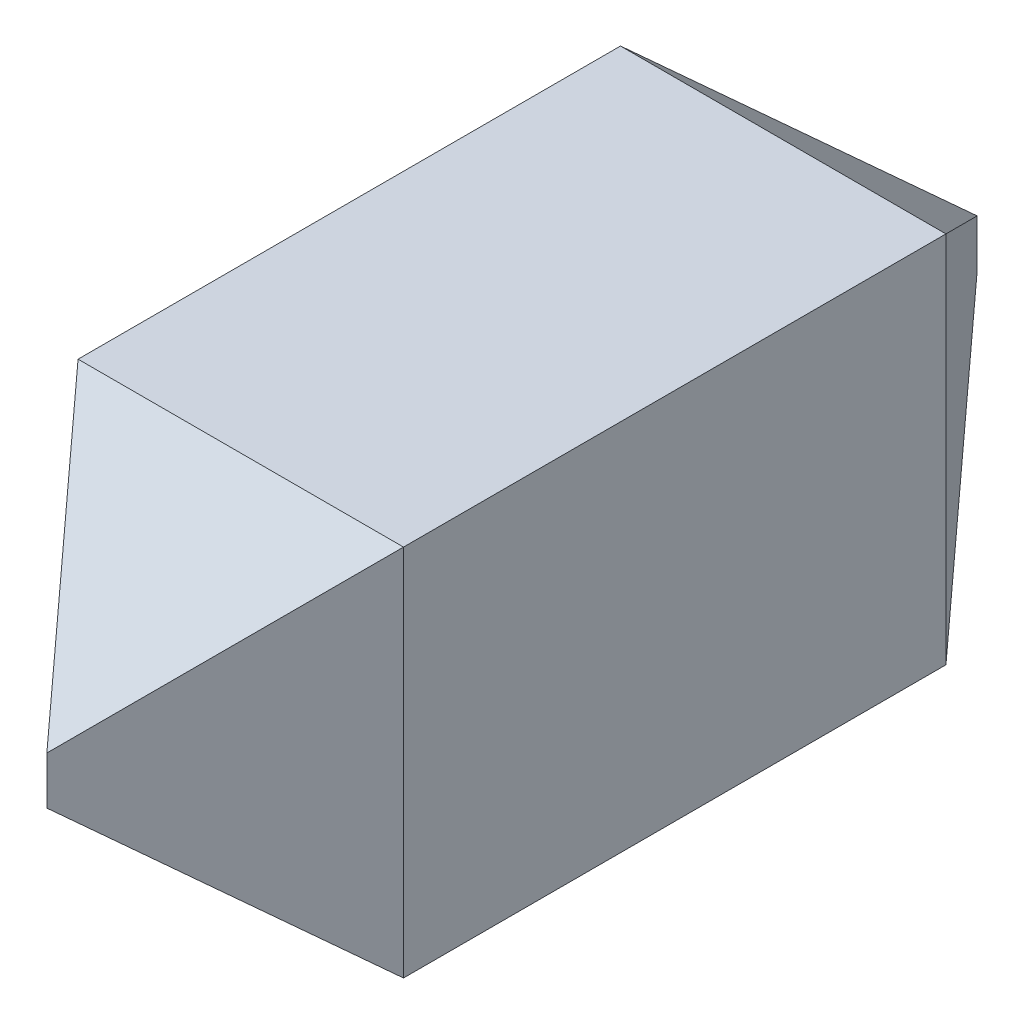
SolidWorks part; units mm, degrees
ref_plane "Front Plane" through (0, 0, 0) normal (0, 0, 1) x (1, 0, 0)
ref_plane "Top Plane" through (0, 0, 0) normal (0, 1, 0) x (1, 0, 0)
ref_plane "Right Plane" through (0, 0, 0) normal (1, 0, 0) x (0, 0, -1)
sketch "Sketch1" plane through (0, 0, 0) normal (0, 0, 1) x (1, 0, 0)
  line L1 (15, -17.2) -> (-15, -17.2)
  line L2 (15, -17.2) -> (15, 17.2)
  line L3 (15, 17.2) -> (-15, 17.2)
  line L4 (-15, -17.2) -> (-15, 17.2)
  line L5 (15, -17.2) -> (-15, 17.2) construction
  line L6 (15, 17.2) -> (-15, -17.2) construction
  point P0 (0, 0)
  dimension "D1" = 30
  dimension "D2" = 34.4
extrude "Boss-Extrude1" add sketch "Sketch1" along normal blind 50
sketch "Sketch2" plane through (0, 0, 50) normal (0, 0, 1) x (1, 0, 0)
  line L1 (15, -17.2) -> (-15, -17.2)
  line L2 (15, -17.2) -> (15, 17.2)
  line L3 (15, 17.2) -> (-15, 17.2)
  line L4 (-15, -17.2) -> (-15, 17.2)
  line L5 (15, -17.2) -> (-15, 17.2) construction
  line L6 (15, 17.2) -> (-15, -17.2) construction
  point P0 (0, 0)
extrude "Boss-Extrude2" add sketch "Sketch2" along normal blind 20 draft 40
sketch "Sketch3" plane through (0, 0, 0) normal (0, 0, -1) x (-1, 0, 0)
  line L1 (15, -17.2) -> (-15, -17.2)
  line L2 (15, -17.2) -> (15, 17.2)
  line L3 (15, 17.2) -> (-15, 17.2)
  line L4 (-15, -17.2) -> (-15, 17.2)
  line L5 (15, -17.2) -> (-15, 17.2) construction
  line L6 (15, 17.2) -> (-15, -17.2) construction
  point P0 (0, 0)
extrude "Boss-Extrude3" add sketch "Sketch3" along normal blind 20 draft 40
